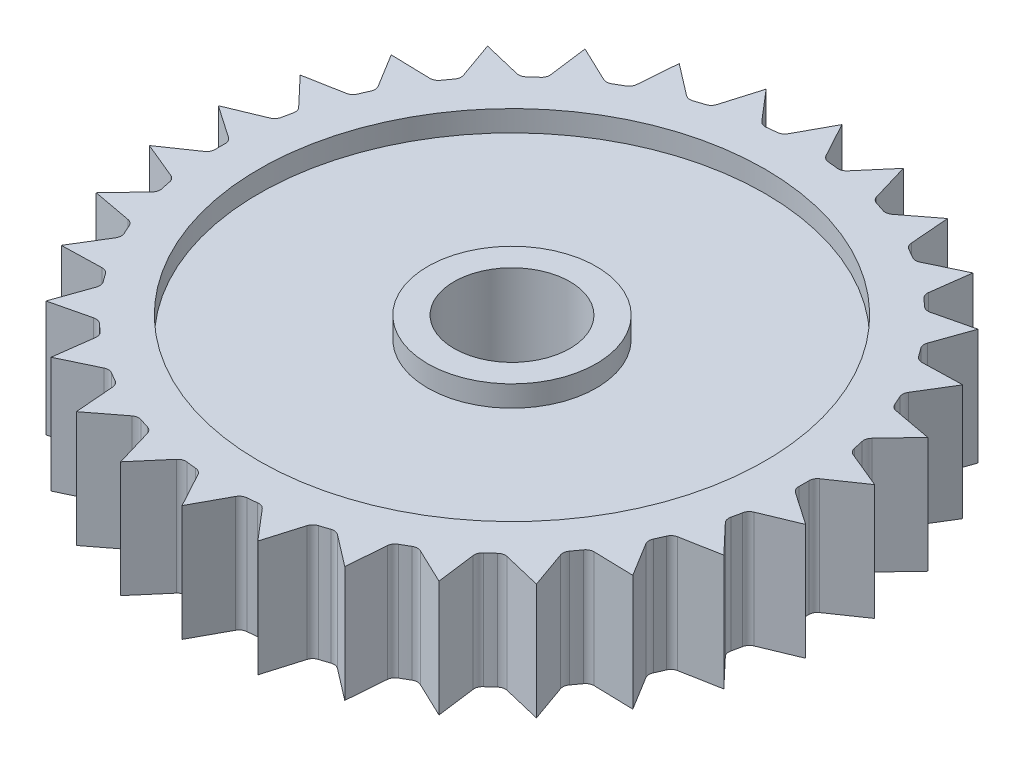
SolidWorks part; units mm, degrees
material "PET"
ref_plane "Front Plane" through (0, 0, 0) normal (0, 0, 1) x (1, 0, 0)
ref_plane "Top Plane" through (0, 0, 0) normal (0, 1, 0) x (1, 0, 0)
ref_plane "Right Plane" through (0, 0, 0) normal (1, 0, 0) x (0, 0, -1)
sketch "Sketch1" plane through (0, 0, 0) normal (0, 1, 0) x (1, 0, 0)
  line L0 (0, 0) -> (0, 18) construction
  line L1 (0, 0) -> (18, 0) construction
  line L2 (0, 0) -> (0, -18) construction
  line L3 (0, 0) -> (-18, 0) construction
  line L4 (0, 15.655) -> (-0.8965, 14.0043)
  line L5 (0, 15.655) -> (0.8965, 14.0043)
  line L8 (3.2549, 15.3129) -> (2.0347, 13.8847)
  line L9 (3.2549, 15.3129) -> (3.7886, 13.5119)
  line L10 (6.3675, 14.3016) -> (4.877, 13.1582)
  line L11 (6.3675, 14.3016) -> (6.5151, 12.4289)
  line L12 (9.2018, 12.6652) -> (7.5062, 11.8567)
  line L13 (9.2018, 12.6652) -> (8.9569, 10.8028)
  line L14 (11.6339, 10.4752) -> (9.8073, 10.037)
  line L15 (11.6339, 10.4752) -> (11.0071, 8.7045)
  line L16 (13.5576, 7.8275) -> (11.6798, 7.7786)
  line L17 (13.5576, 7.8275) -> (12.5764, 6.2257)
  line L18 (14.8888, 4.8377) -> (13.0419, 5.1802)
  line L19 (14.8888, 4.8377) -> (13.596, 3.4749)
  line L20 (15.5692, 1.6364) -> (13.8339, 2.3555)
  line L21 (15.5692, 1.6364) -> (14.0213, 0.5722)
  line L22 (15.5692, -1.6364) -> (14.0213, -0.5722)
  line L23 (15.5692, -1.6364) -> (13.8339, -2.3555)
  line L24 (14.8888, -4.8377) -> (13.596, -3.4749)
  line L25 (14.8888, -4.8377) -> (13.0419, -5.1802)
  line L26 (13.5576, -7.8275) -> (12.5764, -6.2257)
  line L27 (13.5576, -7.8275) -> (11.6798, -7.7786)
  line L28 (11.6339, -10.4752) -> (11.0071, -8.7045)
  line L29 (11.6339, -10.4752) -> (9.8073, -10.037)
  line L30 (9.2018, -12.6652) -> (8.9569, -10.8028)
  line L31 (9.2018, -12.6652) -> (7.5062, -11.8567)
  line L32 (6.3675, -14.3016) -> (6.5151, -12.4289)
  line L33 (6.3675, -14.3016) -> (4.877, -13.1582)
  line L34 (3.2549, -15.3129) -> (3.7886, -13.5119)
  line L35 (3.2549, -15.3129) -> (2.0347, -13.8847)
  line L36 (0, -15.655) -> (0.8965, -14.0043)
  line L37 (0, -15.655) -> (-0.8965, -14.0043)
  line L38 (-3.2549, -15.3129) -> (-2.0347, -13.8847)
  line L39 (-3.2549, -15.3129) -> (-3.7886, -13.5119)
  line L40 (-6.3675, -14.3016) -> (-4.877, -13.1582)
  line L41 (-6.3675, -14.3016) -> (-6.5151, -12.4289)
  line L42 (-9.2018, -12.6652) -> (-7.5062, -11.8567)
  line L43 (-9.2018, -12.6652) -> (-8.9569, -10.8028)
  line L44 (-11.6339, -10.4752) -> (-9.8073, -10.037)
  line L45 (-11.6339, -10.4752) -> (-11.0071, -8.7045)
  line L46 (-13.5576, -7.8275) -> (-11.6798, -7.7786)
  line L47 (-13.5576, -7.8275) -> (-12.5764, -6.2257)
  line L48 (-14.8888, -4.8377) -> (-13.0419, -5.1802)
  line L49 (-14.8888, -4.8377) -> (-13.596, -3.4749)
  line L50 (-15.5692, -1.6364) -> (-13.8339, -2.3555)
  line L51 (-15.5692, -1.6364) -> (-14.0213, -0.5722)
  line L52 (-15.5692, 1.6364) -> (-14.0213, 0.5722)
  line L53 (-15.5692, 1.6364) -> (-13.8339, 2.3555)
  line L54 (-14.8888, 4.8377) -> (-13.596, 3.4749)
  line L55 (-14.8888, 4.8377) -> (-13.0419, 5.1802)
  line L56 (-13.5576, 7.8275) -> (-12.5764, 6.2257)
  line L57 (-13.5576, 7.8275) -> (-11.6798, 7.7786)
  line L58 (-11.6339, 10.4752) -> (-11.0071, 8.7045)
  line L59 (-11.6339, 10.4752) -> (-9.8073, 10.037)
  line L60 (-9.2018, 12.6652) -> (-8.9569, 10.8028)
  line L61 (-9.2018, 12.6652) -> (-7.5062, 11.8567)
  line L62 (-6.3675, 14.3016) -> (-6.5151, 12.4289)
  line L63 (-6.3675, 14.3016) -> (-4.877, 13.1582)
  line L64 (-3.2549, 15.3129) -> (-3.7886, 13.5119)
  line L65 (-3.2549, 15.3129) -> (-2.0347, 13.8847)
  arc A0 (-1.213, 13.7968) -> (-1.682, 13.7475) centre (0, 0) ccw
  circle A1 centre (0, 0) radius 15.655 construction
  arc A2 (0.8965, 14.0043) -> (1.213, 13.7968) centre (1.248, 14.1952) ccw
  arc A3 (-0.8965, 14.0043) -> (-1.213, 13.7968) centre (-1.248, 14.1952) cw
  arc A4 (3.7886, 13.5119) -> (4.055, 13.2431) centre (4.1721, 13.6256) ccw
  arc A5 (2.0347, 13.8847) -> (1.682, 13.7475) centre (1.7306, 14.1445) cw
  arc A6 (6.5151, 12.4289) -> (6.7198, 12.1106) centre (6.9139, 12.4604) ccw
  arc A7 (4.877, 13.1582) -> (4.5035, 13.0974) centre (4.6336, 13.4756) cw
  arc A8 (8.9569, 10.8028) -> (9.0909, 10.4488) centre (9.3534, 10.7506) ccw
  arc A9 (7.5062, 11.8567) -> (7.1282, 11.8748) centre (7.3341, 12.2178) cw
  arc A10 (11.0071, 8.7045) -> (11.0647, 8.3304) centre (11.3842, 8.571) ccw
  arc A11 (9.8073, 10.037) -> (9.4413, 10.1333) centre (9.714, 10.4259) cw
  arc A12 (12.5764, 6.2257) -> (12.5549, 5.8479) centre (12.9175, 6.0168) ccw
  arc A13 (11.6798, 7.7786) -> (11.3419, 7.9489) centre (11.6694, 8.1785) cw
  arc A14 (13.596, 3.4749) -> (13.4964, 3.1098) centre (13.8861, 3.1996) ccw
  arc A15 (13.0419, 5.1802) -> (12.7467, 5.4171) centre (13.1148, 5.5735) cw
  arc A16 (14.0213, 0.5722) -> (13.848, 0.2358) centre (14.2479, 0.2426) ccw
  arc A17 (13.8339, 2.3555) -> (13.5944, 2.6485) centre (13.987, 2.725) cw
  arc A18 (13.8339, -2.3555) -> (13.5944, -2.6485) centre (13.987, -2.725) ccw
  arc A19 (14.0213, -0.5722) -> (13.848, -0.2358) centre (14.2479, -0.2426) cw
  arc A20 (13.0419, -5.1802) -> (12.7467, -5.4171) centre (13.1148, -5.5735) ccw
  arc A21 (13.596, -3.4749) -> (13.4964, -3.1098) centre (13.8861, -3.1996) cw
  arc A22 (11.6798, -7.7786) -> (11.3419, -7.9489) centre (11.6694, -8.1785) ccw
  arc A23 (12.5764, -6.2257) -> (12.5549, -5.8479) centre (12.9175, -6.0168) cw
  arc A24 (9.8073, -10.037) -> (9.4413, -10.1333) centre (9.714, -10.4259) ccw
  arc A25 (11.0071, -8.7045) -> (11.0647, -8.3304) centre (11.3842, -8.571) cw
  arc A26 (7.5062, -11.8567) -> (7.1282, -11.8748) centre (7.3341, -12.2178) ccw
  arc A27 (8.9569, -10.8028) -> (9.0909, -10.4488) centre (9.3534, -10.7506) cw
  arc A28 (4.877, -13.1582) -> (4.5035, -13.0974) centre (4.6336, -13.4756) ccw
  arc A29 (6.5151, -12.4289) -> (6.7198, -12.1106) centre (6.9139, -12.4604) cw
  arc A30 (2.0347, -13.8847) -> (1.682, -13.7475) centre (1.7306, -14.1445) ccw
  arc A31 (3.7886, -13.5119) -> (4.055, -13.2431) centre (4.1721, -13.6256) cw
  arc A32 (-0.8965, -14.0043) -> (-1.213, -13.7968) centre (-1.248, -14.1952) ccw
  arc A33 (0.8965, -14.0043) -> (1.213, -13.7968) centre (1.248, -14.1952) cw
  arc A34 (-3.7886, -13.5119) -> (-4.055, -13.2431) centre (-4.1721, -13.6256) ccw
  arc A35 (-2.0347, -13.8847) -> (-1.682, -13.7475) centre (-1.7306, -14.1445) cw
  arc A36 (-6.5151, -12.4289) -> (-6.7198, -12.1106) centre (-6.9139, -12.4604) ccw
  arc A37 (-4.877, -13.1582) -> (-4.5035, -13.0974) centre (-4.6336, -13.4756) cw
  arc A38 (-8.9569, -10.8028) -> (-9.0909, -10.4488) centre (-9.3534, -10.7506) ccw
  arc A39 (-7.5062, -11.8567) -> (-7.1282, -11.8748) centre (-7.3341, -12.2178) cw
  arc A40 (-11.0071, -8.7045) -> (-11.0647, -8.3304) centre (-11.3842, -8.571) ccw
  arc A41 (-9.8073, -10.037) -> (-9.4413, -10.1333) centre (-9.714, -10.4259) cw
  arc A42 (-12.5764, -6.2257) -> (-12.5549, -5.8479) centre (-12.9175, -6.0168) ccw
  arc A43 (-11.6798, -7.7786) -> (-11.3419, -7.9489) centre (-11.6694, -8.1785) cw
  arc A44 (-13.596, -3.4749) -> (-13.4964, -3.1098) centre (-13.8861, -3.1996) ccw
  arc A45 (-13.0419, -5.1802) -> (-12.7467, -5.4171) centre (-13.1148, -5.5735) cw
  arc A46 (-14.0213, -0.5722) -> (-13.848, -0.2358) centre (-14.2479, -0.2426) ccw
  arc A47 (-13.8339, -2.3555) -> (-13.5944, -2.6485) centre (-13.987, -2.725) cw
  arc A48 (-13.8339, 2.3555) -> (-13.5944, 2.6485) centre (-13.987, 2.725) ccw
  arc A49 (-14.0213, 0.5722) -> (-13.848, 0.2358) centre (-14.2479, 0.2426) cw
  arc A50 (-13.0419, 5.1802) -> (-12.7467, 5.4171) centre (-13.1148, 5.5735) ccw
  arc A51 (-13.596, 3.4749) -> (-13.4964, 3.1098) centre (-13.8861, 3.1996) cw
  arc A52 (-11.6798, 7.7786) -> (-11.3419, 7.9489) centre (-11.6694, 8.1785) ccw
  arc A53 (-12.5764, 6.2257) -> (-12.5549, 5.8479) centre (-12.9175, 6.0168) cw
  arc A54 (-9.8073, 10.037) -> (-9.4413, 10.1333) centre (-9.714, 10.4259) ccw
  arc A55 (-11.0071, 8.7045) -> (-11.0647, 8.3304) centre (-11.3842, 8.571) cw
  arc A56 (-7.5062, 11.8567) -> (-7.1282, 11.8748) centre (-7.3341, 12.2178) ccw
  arc A57 (-8.9569, 10.8028) -> (-9.0909, 10.4488) centre (-9.3534, 10.7506) cw
  arc A58 (-4.877, 13.1582) -> (-4.5035, 13.0974) centre (-4.6336, 13.4756) ccw
  arc A59 (-6.5151, 12.4289) -> (-6.7198, 12.1106) centre (-6.9139, 12.4604) cw
  arc A60 (-2.0347, 13.8847) -> (-1.682, 13.7475) centre (-1.7306, 14.1445) ccw
  arc A61 (-3.7886, 13.5119) -> (-4.055, 13.2431) centre (-4.1721, 13.6256) cw
  arc A62 (-4.055, 13.2431) -> (-4.5035, 13.0974) centre (0, 0) ccw
  arc A63 (-6.7198, 12.1106) -> (-7.1282, 11.8748) centre (0, 0) ccw
  arc A64 (-9.0909, 10.4488) -> (-9.4413, 10.1333) centre (0, 0) ccw
  arc A65 (-11.0647, 8.3304) -> (-11.3419, 7.9489) centre (0, 0) ccw
  arc A66 (-12.5549, 5.8479) -> (-12.7467, 5.4171) centre (0, 0) ccw
  arc A67 (-13.4964, 3.1098) -> (-13.5944, 2.6485) centre (0, 0) ccw
  arc A68 (-13.848, 0.2358) -> (-13.848, -0.2358) centre (0, 0) ccw
  arc A69 (-13.5944, -2.6485) -> (-13.4964, -3.1098) centre (0, 0) ccw
  arc A70 (-12.7467, -5.4171) -> (-12.5549, -5.8479) centre (0, 0) ccw
  arc A71 (-11.3419, -7.9489) -> (-11.0647, -8.3304) centre (0, 0) ccw
  arc A72 (-9.4413, -10.1333) -> (-9.0909, -10.4488) centre (0, 0) ccw
  arc A73 (-7.1282, -11.8748) -> (-6.7198, -12.1106) centre (0, 0) ccw
  arc A74 (-4.5035, -13.0974) -> (-4.055, -13.2431) centre (0, 0) ccw
  arc A75 (-1.682, -13.7475) -> (-1.213, -13.7968) centre (0, 0) ccw
  arc A76 (1.213, -13.7968) -> (1.682, -13.7475) centre (0, 0) ccw
  arc A77 (4.055, -13.2431) -> (4.5035, -13.0974) centre (0, 0) ccw
  arc A78 (6.7198, -12.1106) -> (7.1282, -11.8748) centre (0, 0) ccw
  arc A79 (9.0909, -10.4488) -> (9.4413, -10.1333) centre (0, 0) ccw
  arc A80 (11.0647, -8.3304) -> (11.3419, -7.9489) centre (0, 0) ccw
  arc A81 (12.5549, -5.8479) -> (12.7467, -5.4171) centre (0, 0) ccw
  arc A82 (13.4964, -3.1098) -> (13.5944, -2.6485) centre (0, 0) ccw
  arc A83 (13.848, -0.2358) -> (13.848, 0.2358) centre (0, 0) ccw
  arc A84 (12.7467, 5.4171) -> (12.5549, 5.8479) centre (0, 0) ccw
  arc A85 (13.5944, 2.6485) -> (13.4964, 3.1098) centre (0, 0) ccw
  arc A86 (11.3419, 7.9489) -> (11.0647, 8.3304) centre (0, 0) ccw
  arc A87 (9.4413, 10.1333) -> (9.0909, 10.4488) centre (0, 0) ccw
  arc A88 (7.1282, 11.8748) -> (6.7198, 12.1106) centre (0, 0) ccw
  arc A89 (4.5035, 13.0974) -> (4.055, 13.2431) centre (0, 0) ccw
  arc A90 (1.682, 13.7475) -> (1.213, 13.7968) centre (0, 0) ccw
  point P12 (1, 13.8139)
  point P15 (-1, 13.8139)
  point P222 (0, 0)
  dimension "D1" = 31.31
  dimension "D2" = 27.7
  dimension "D6" = 0.4
  dimension "D3" = 18
  dimension "D4" = 2
  dimension "D5" = 28.508
extrude "Boss-Extrude1" add sketch "Sketch1" along normal blind 5.5
sketch "Sketch2" plane through (0, 5.5, 0) normal (0, 1, 0) x (1, 0, 0)
  circle A0 centre (0, 0) radius 2.75
  circle A1 centre (0, 0) radius 4
  circle A2 centre (0, 0) radius 12
  dimension "D1" = 5.5
  dimension "D2" = 8
  dimension "D3" = 24
extrude "Cut-Extrude1" cut sketch "Sketch2" against normal through all contours A0 region at (0, 5.5, 0)
extrude "Cut-Extrude2" cut sketch "Sketch2<3>" against normal blind 1 contours A2 A1 region at (-11.6606, 5.5, 0)
sketch "Sketch2<3>" plane through (0, 5.5, 0) normal (0, 1, 0) x (1, 0, 0) same geometry as "Sketch2"
sketch "Sketch3" plane through (0, 0, 0) normal (0, -1, 0) x (1, 0, 0)
  circle A0 centre (0, 0) radius 4
  circle A1 centre (0, 0) radius 12
  dimension "D1" = 8
  dimension "D2" = 24
extrude "Cut-Extrude3" cut sketch "Sketch3" against normal blind 1
sketch "Sketch4" plane through (0, 5.5, 0) normal (0, 1, 0) x (1, 0, 0)
  circle A0 centre (0, 0) radius 15
  dimension "D1" = 30
